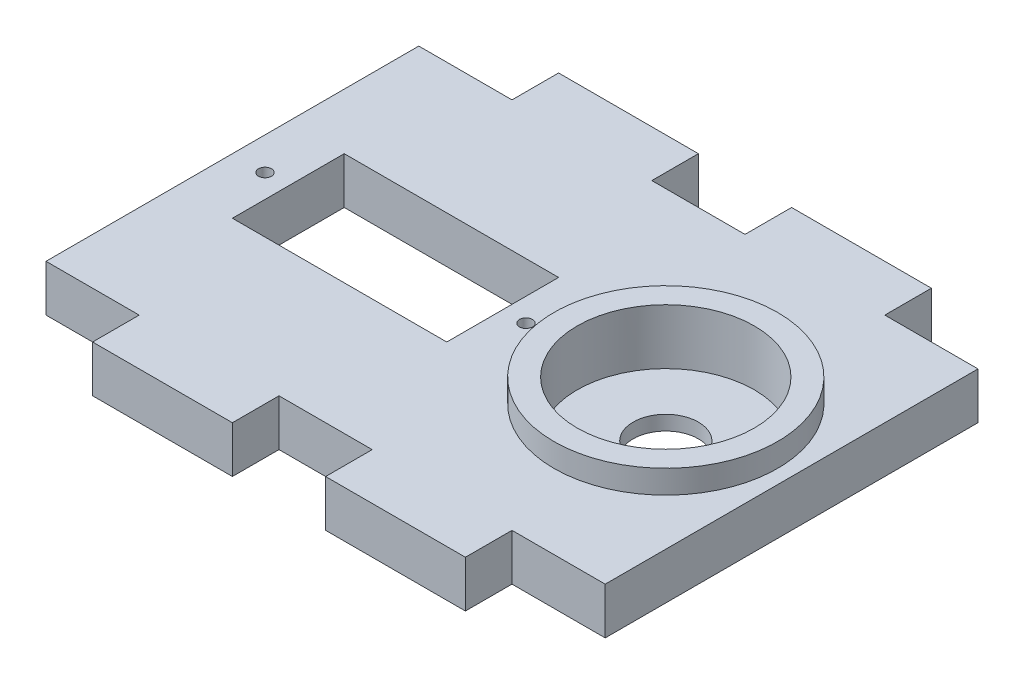
SolidWorks part; units mm, degrees
ref_plane "Front Plane" through (0, 0, 0) normal (0, 0, 1) x (1, 0, 0)
ref_plane "Top Plane" through (0, 0, 0) normal (0, 1, 0) x (1, 0, 0)
ref_plane "Right Plane" through (0, 0, 0) normal (1, 0, 0) x (0, 0, -1)
sketch "Sketch1" plane through (0, 0, 0) normal (0, 1, 0) x (1, 0, 0)
  line L0 (7.5, 20) -> (17.5, 20)
  line L1 (-17.5, -20) -> (-7.5, -20)
  line L2 (-17.5, -20) -> (-17.5, 20)
  line L3 (-17.5, 20) -> (-7.5, 20)
  line L4 (42.5, -20) -> (42.5, 20)
  line L5 (32.5, 20) -> (42.5, 20)
  line L7 (-11.5, -6) -> (11.5, -6)
  line L8 (-11.5, -6) -> (-11.5, 6)
  line L9 (-11.5, 6) -> (11.5, 6)
  line L10 (11.5, -6) -> (11.5, 6)
  line L11 (32.5, 20) -> (32.5, 25)
  line L12 (32.5, 25) -> (17.5, 25)
  line L14 (-7.5, 20) -> (-7.5, 25)
  line L15 (-7.5, 25) -> (7.5, 25)
  line L16 (7.5, 20) -> (7.5, 25)
  line L18 (-7.5, -20) -> (-7.5, -25)
  line L19 (-7.5, -25) -> (7.5, -25)
  line L20 (7.5, -20) -> (7.5, -25)
  line L21 (7.5, -20) -> (17.5, -20)
  line L22 (17.5, 20) -> (17.5, 25)
  line L24 (32.5, -20) -> (32.5, -25)
  line L25 (32.5, -25) -> (17.5, -25)
  line L26 (17.5, -20) -> (17.5, -25)
  line L27 (32.5, -20) -> (42.5, -20)
  circle A0 centre (-14, 0) radius 0.7
  circle A1 centre (14, 0) radius 0.7
  circle A2 centre (29, 0) radius 9.5
  point P0 (0, 0)
  point P10 (0, 0)
  dimension "D6" = 1.4
  dimension "D7" = 1.4
  dimension "D15" = 19
  dimension "D17" = 10
  dimension "D1" = 40
  dimension "D2" = 28
  dimension "D3" = 14
  dimension "D4" = 12
  dimension "D5" = 23
  dimension "D8" = 60
  dimension "D9" = 15
  dimension "D10" = 10
  dimension "D11" = 5
  dimension "D12" = 5
  dimension "D13" = 20
  dimension "D14" = 10
  dimension "D16" = 15
  dimension "D18" = 15
  dimension "D19" = 10
extrude "Boss-Extrude1" add sketch "Sketch1" along normal blind 5
sketch "Sketch2" plane through (0, 5, 0) normal (0, 1, 0) x (1, 0, 0)
  circle A0 centre (29, 0) radius 12
  circle A1 centre (29, 0) radius 9.5 construction
  circle A2 centre (29, 0) radius 9.5
  dimension "D1" = 2.5
extrude "Boss-Extrude2" add sketch "Sketch2" along normal blind 2.5
sketch "Sketch3" plane through (0, 0, 0) normal (0, -1, 0) x (1, 0, 0)
  circle A2 centre (29, 0) radius 9.5
  circle A3 centre (29, 0) radius 3.5
extrude "Boss-Extrude3" add sketch "Sketch3" against normal blind 1.56
